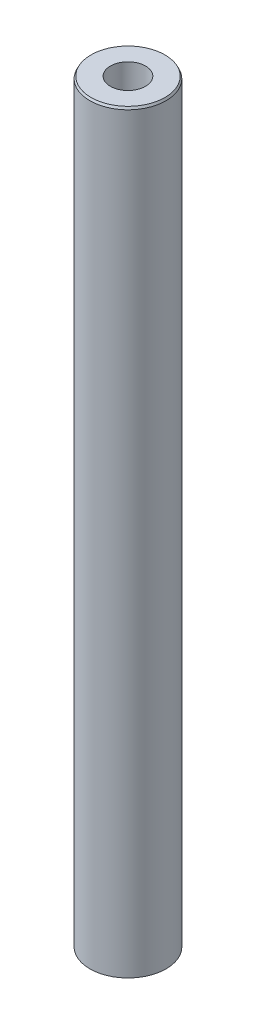
SolidWorks part; units mm, degrees
ref_plane "Front Plane" through (0, 0, 0) normal (0, 0, 1) x (1, 0, 0)
ref_plane "Top Plane" through (0, 0, 0) normal (0, 1, 0) x (1, 0, 0)
ref_plane "Right Plane" through (0, 0, 0) normal (1, 0, 0) x (0, 0, -1)
sketch "Sketch1" plane through (0, 0, 0) normal (0, 1, 0) x (1, 0, 0)
  circle A0 centre (0, 0) radius 5
  dimension "SHAFT_OD" = 10
extrude "Boss-Extrude1" add sketch "Sketch1" along normal blind 99.127
sketch "Sketch2" plane through (0, 0, 0) normal (0, 1, 0) x (1, 0, 0)
  circle A0 centre (0, 0) radius 2.3101
  dimension "BORE_D" = 4.6201
extrude "Cut-Extrude1" cut sketch "Sketch2" along normal through all
chamfer "Chamfer1" distance 0.2913 angle 27.325 2 edges at (0, 99.127, 5) (0, 0, 5) first distance on face at (0, 99.127, 5) first distance on face at (0, 0, 2.3101)
